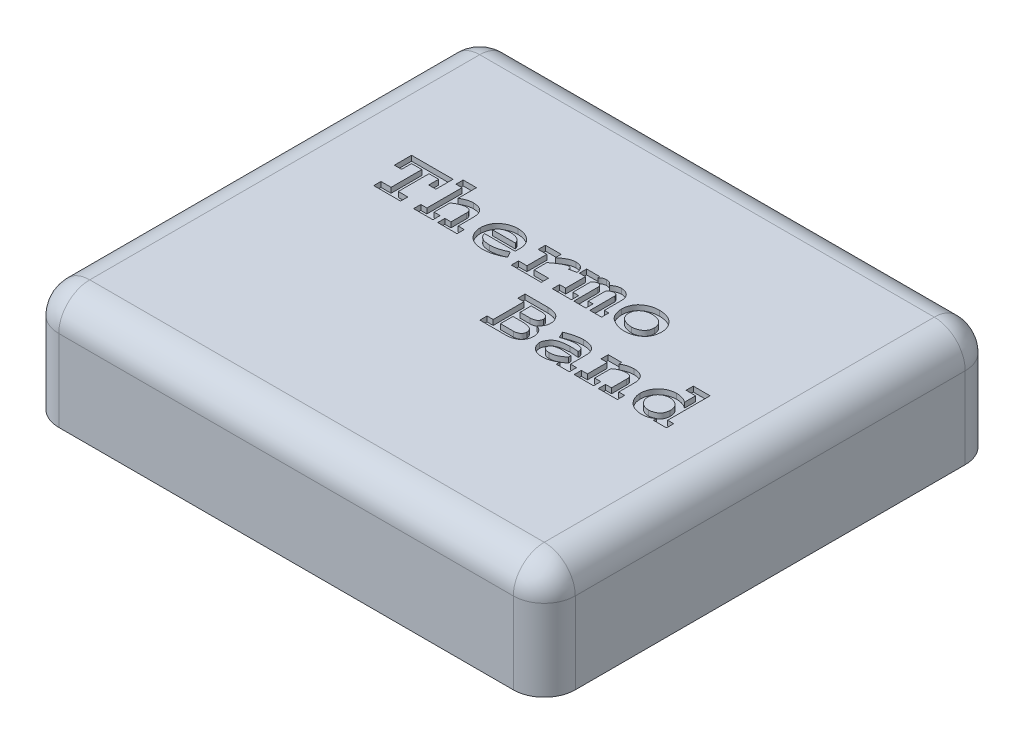
SolidWorks part; units mm, degrees
note: '?' marks a value the reader was unsure of.
ref_plane "Front Plane" through (0, 0, 0) normal (0, 0, 1) x (1, 0, 0)
ref_plane "Top Plane" through (0, 0, 0) normal (0, 1, 0) x (1, 0, 0)
ref_plane "Right Plane" through (0, 0, 0) normal (1, 0, 0) x (0, 0, -1)
ref_axis "Axis1" through (0, -5.35, 0) along (0, 1, 0)?
sketch "Sketch1" plane through (0, 0, 0) normal (0, 1, 0) x (1, 0, 0)
  line L1 (-20, -17.5) -> (20, -17.5)
  line L2 (-20, -17.5) -> (-20, 17.5)
  line L3 (-20, 17.5) -> (20, 17.5)
  line L4 (20, -17.5) -> (20, 17.5)
  line L5 (-20, -17.5) -> (20, 17.5) construction
  line L6 (-20, 17.5) -> (20, -17.5) construction
  point P0 (0, 0)
  dimension "D1" = 35
  dimension "D2" = 40
extrude "Boss-Extrude1" add sketch "Sketch1" along normal blind 2 and the other way blind 6.7
sketch "Sketch2" plane through (0, -6.7, 0) normal (0, -1, 0) x (1, 0, 0)
  line L8 (18, -15.5) -> (18, 15.5)
  line L9 (18, 15.5) -> (-18, 15.5)
  line L10 (-18, 15.5) -> (-18, -15.5)
  line L11 (-18, -15.5) -> (18, -15.5)
  line L12 (18, -15.5) -> (18, 15.5)
  line L13 (18, 15.5) -> (-18, 15.5)
  line L14 (-18, 15.5) -> (-18, -15.5)
  line L15 (-18, -15.5) -> (18, -15.5)
  dimension "D1" = 2
extrude "Cut-Extrude1" cut sketch "Sketch2" against normal offset from surface (6.7 mm away) 2 up to face at (0, 2, 0)
sketch "Sketch3" plane through (0, -6.7, 0) normal (0, -1, 0) x (1, 0, 0)
  line L0 (-20, -17.5) -> (-20, 17.5) construction
  line L1 (20, -17.5) -> (-20, -17.5) construction
  circle A0 centre (-17.5, -15) radius 2.5
  dimension "D1" = 5
extrude "Boss-Extrude2" add sketch "Sketch3" against normal up to surface (6.7 mm away) contours A0 up to face at (0, 0, 0)
sketch "Sketch4" plane through (0, -6.7, 0) normal (0, -1, 0) x (1, 0, 0)
  circle A0 centre (-17.5, -15) radius 1.25
  dimension "D1" = 2.5
extrude "Cut-Extrude2" cut sketch "Sketch4" against normal blind 3 draft 11 contours A0
mirror "Mirror1" about plane through (0, 0, 0) normal (1, 0, 0) of "Boss-Extrude2"
mirror "Mirror2" about plane through (0, 0, 0) normal (0, 0, 1) of "Boss-Extrude2", "Mirror1"
sketch "Sketch5" plane through (0, -6.7, 0) normal (0, -1, 0) x (1, 0, 0)
  circle A0 centre (17.5, -15) radius 1.25
  dimension "D1" = 2.5
extrude "Cut-Extrude3" cut sketch "Sketch5" against normal offset from surface (6.7 mm away) 2 contours A0 up to face at (0, 2, 0)
pattern_circular "CirPattern1" count 2 every 180 about axis through (0, 0, 0) along (0, 1, 0) of "Cut-Extrude2", "Cut-Extrude3"
fillet "Fillet1" radius 2.4 8 edges at (0, 2, 17.5) (-20, 2, 0) (0, 2, -17.5) (20, 2, 0) (-20, -2.35, -17.5) (-20, -2.35, 17.5) (20, -2.35, 17.5) (20, -2.35, -17.5)
sketch "Sketch6" plane through (-20, 0, 0) normal (-1, 0, 0) x (0, 0, 1)
  line L12 (2.3332, -6.7038) -> (5.4032, -6.7038)
  line L13 (6.6032, -5.5038) -> (6.6032, -4.2938)
  line L14 (5.4032, -3.0938) -> (-1.5368, -3.0938)
  line L15 (-2.7368, -4.2938) -> (-2.7368, -5.5038)
  line L16 (-1.5368, -6.7038) -> (2.2832, -6.7038)
  line L17 (2.2832, -6.7038) -> (2.3332, -6.7038)
  line L18 (2.3332, -6.7038) -> (5.4032, -6.7038)
  line L19 (6.6032, -5.5038) -> (6.6032, -4.2938)
  line L20 (5.4032, -3.0938) -> (-1.5368, -3.0938)
  line L21 (-2.7368, -4.2938) -> (-2.7368, -5.5038)
  line L22 (-1.5368, -6.7038) -> (2.2832, -6.7038)
  line L23 (2.2832, -6.7038) -> (2.3332, -6.7038)
  arc A8 (5.4032, -6.7038) -> (6.6032, -5.5038) centre (5.4032, -5.5038) ccw
  arc A9 (6.6032, -4.2938) -> (5.4032, -3.0938) centre (5.4032, -4.2938) ccw
  arc A10 (-1.5368, -3.0938) -> (-2.7368, -4.2938) centre (-1.5368, -4.2938) ccw
  arc A11 (-2.7368, -5.5038) -> (-1.5368, -6.7038) centre (-1.5368, -5.5038) ccw
  arc A12 (5.4032, -6.7038) -> (6.6032, -5.5038) centre (5.4032, -5.5038) ccw
  arc A13 (6.6032, -4.2938) -> (5.4032, -3.0938) centre (5.4032, -4.2938) ccw
  arc A14 (-1.5368, -3.0938) -> (-2.7368, -4.2938) centre (-1.5368, -4.2938) ccw
  arc A15 (-2.7368, -5.5038) -> (-1.5368, -6.7038) centre (-1.5368, -5.5038) ccw
  dimension "D1" = 0.2
extrude "Cut-Extrude4" cut sketch "Sketch6" against normal up to next
sketch "Sketch9" plane through (0, -6.7, 0) normal (0, -1, 0) x (1, 0, 0)
  line L0 (-18, -1.6317) -> (-18, -12.5505) construction
  line L1 (-15.667, -13.3) -> (-18, -13.3)
  line L2 (-15.667, -13.3) -> (-15.667, -12.5)
  line L3 (-15.667, -12.5) -> (-18, -12.5)
  line L4 (-18, -13.3) -> (-18, -12.5)
  arc A0 (-15.0505, -15.5) -> (-18, -12.5505) centre (-17.5, -15) ccw construction
  dimension "D1" = 0.8
extrude "Cut-Extrude5" cut sketch "Sketch9" against normal blind 4
mirror "Mirror3" about plane through (0, 0, 0) normal (1, 0, 0) of "Cut-Extrude5"
sketch "Sketch10" plane through (0, 2, 0) normal (0, 1, 0) x (1, 0, 0)
  text T0 "Thermo" font "Courier Std" height 3.5
  text T1 "Band" font "Courier Std" height 3.5
extrude "Cut-Extrude6" cut sketch "Sketch10" against normal blind 0.4
